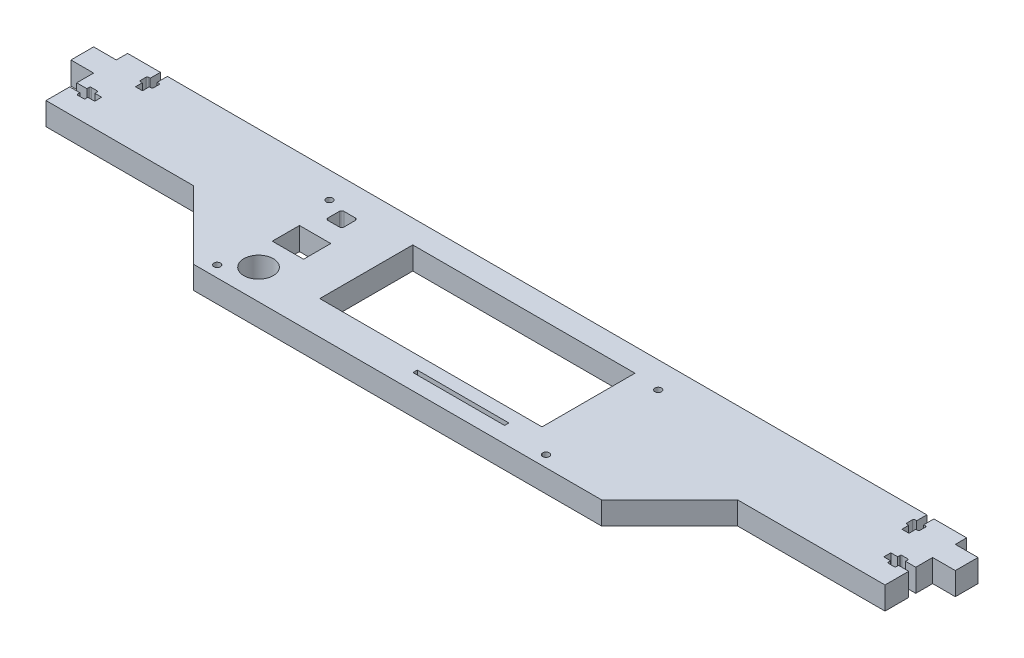
SolidWorks part; units mm, degrees
ref_plane "Front Plane" through (0, 0, 0) normal (0, 0, 1) x (1, 0, 0)
ref_plane "Top Plane" through (0, 0, 0) normal (0, 1, 0) x (1, 0, 0)
ref_plane "Right Plane" through (0, 0, 0) normal (1, 0, 0) x (0, 0, -1)
sketch "Sketch1" plane through (0, 0, 0) normal (0, 1, 0) x (1, 0, 0)
  line L0 (0, 18) -> (0, -18) construction
  line L1 (-185, 18) -> (0, 18)
  line L2 (-185, 18) -> (-185, 13)
  line L3 (-185, -18) -> (0, -18)
  line L4 (0, 18) -> (0, -18)
  line L5 (-185, 18) -> (0, 0) construction
  line L6 (-185, -18) -> (0, 0) construction
  line L7 (-185, 13) -> (-195, 13)
  line L8 (-195, 13) -> (-195, 3)
  line L9 (-195, 3) -> (-185, 3)
  line L10 (-185, 3) -> (-185, -18)
  point P0 (0, 0)
  dimension "D6" = 10
  dimension "D7" = 10
  dimension "D1" = 185
  dimension "D2" = 36
  dimension "D4" = 5
  dimension "D9" = 18
extrude "MainShape" add sketch "Sketch1" along normal blind 10 contours L2 L7 L8 L9 region at (-93.9423, 0, -0.1183)
sketch "Sketch2" plane through (0, 10, 0) normal (0, 1, 0) x (1, 0, 0)
  line L0 (-169, 18) -> (-169, 7) construction
  line L1 (-185, 18) -> (0, 18) construction
  line L2 (-170.55, 18) -> (-170.55, 13.5)
  line L3 (-170.55, 13.5) -> (-171.35, 13.5)
  line L4 (-171.85, 13) -> (-171.85, 10.5)
  line L5 (-171.35, 10) -> (-170.55, 10)
  line L6 (-170.55, 10) -> (-170.55, 7)
  line L7 (-170.55, 7) -> (-167.45, 7)
  line L8 (-185, 18) -> (-185, 13) construction
  line L9 (-170.55, 18) -> (-167.45, 18)
  line L10 (-167.45, 10) -> (-167.45, 7)
  line L11 (-166.65, 10) -> (-167.45, 10)
  line L12 (-166.15, 13) -> (-166.15, 10.5)
  line L13 (-167.45, 13.5) -> (-166.65, 13.5)
  line L14 (-167.45, 18) -> (-167.45, 13.5)
  line L16 (-185, -6) -> (-174, -6) construction
  line L50 (-185, 3) -> (-185, -18) construction
  line L51 (-174, -7.55) -> (-174, -4.45)
  line L52 (-174, -4.45) -> (-177, -4.45)
  line L53 (-177, -4.45) -> (-177, -3.5)
  line L54 (-177.5, -3) -> (-180, -3)
  line L55 (-180.5, -3.5) -> (-180.5, -4.45)
  line L56 (-180.5, -4.45) -> (-185, -4.45)
  line L57 (-185, -4.45) -> (-185, -7.55)
  line L58 (-195, 13) -> (-195, 3) construction
  line L59 (-180.5, -7.55) -> (-185, -7.55)
  line L60 (-180.5, -8.5) -> (-180.5, -7.55)
  line L61 (-177.5, -9) -> (-180, -9)
  line L62 (-177, -7.55) -> (-177, -8.5)
  line L63 (-174, -7.55) -> (-177, -7.55)
  arc A0 (-171.85, 10.5) -> (-171.35, 10) centre (-171.35, 10.5) ccw
  arc A1 (-171.35, 13.5) -> (-171.85, 13) centre (-171.35, 13) ccw
  arc A2 (-166.65, 13.5) -> (-166.15, 13) centre (-166.65, 13) cw
  arc A3 (-166.15, 10.5) -> (-166.65, 10) centre (-166.65, 10.5) cw
  arc A16 (-177, -3.5) -> (-177.5, -3) centre (-177.5, -3.5) ccw
  arc A17 (-180, -3) -> (-180.5, -3.5) centre (-180, -3.5) ccw
  arc A18 (-180, -9) -> (-180.5, -8.5) centre (-180, -8.5) cw
  arc A19 (-177, -8.5) -> (-177.5, -9) centre (-177.5, -8.5) cw
  point P14 (-171.85, 10)
  point P17 (-171.85, 13.5)
  point P28 (-166.15, 13.5)
  point P29 (-166.15, 10)
  point P34 (-195, 8)
  point P45 (-177, -3)
  point P48 (-180.5, -3)
  dimension "D8" = 0.5
  dimension "D16" = 0.5
  dimension "D1" = 11
  dimension "D2" = 1.55
  dimension "D3" = 1.55
  dimension "D4" = 8
  dimension "D5" = 2.85
  dimension "D6" = 3.5
  dimension "D7" = 16
  dimension "D9" = 11
  dimension "D10" = 8
  dimension "D11" = 3.5
  dimension "D12" = 3
  dimension "D13" = 1.55
  dimension "D14" = 1.55
  dimension "D15" = 14
extrude "ScrewSlots" cut sketch "Sketch2" against normal through all
mirror "Mirror1" about plane through (0, 0, 0) normal (1, 0, 0) of "ScrewSlots", "MainShape"
sketch "Sketch6" plane through (0, 10, 0) normal (0, 1, 0) x (1, 0, 0)
  line L0 (0, -18) -> (0, -48) construction
  line L2 (-185, -18) -> (185, -18) construction
  line L3 (90, -48) -> (-90, -48)
  line L4 (-90, -48) -> (-120, -18)
  line L5 (90, -48) -> (120, -18)
  line L6 (-120, -18) -> (120, -18)
  dimension "D1" = 135
  dimension "D2" = 30
  dimension "D3" = 90
extrude "Boss-Extrude1" add sketch "Sketch6" against normal through all
sketch "Sketch8" plane through (0, 10, 0) normal (0, 1, 0) x (1, 0, 0)
  line L0 (-71.5, 4.8833) -> (-77.5, 4.8833) construction
  line L1 (-77, -1.6167) -> (-72, -1.6167)
  line L2 (-78, -0.6167) -> (-78, 4.3833)
  line L3 (-77, 5.3833) -> (-72, 5.3833)
  line L4 (-71, -0.6167) -> (-71, 4.3833)
  line L5 (-78, -1.6167) -> (-71, 5.3833) construction
  line L6 (-78, 5.3833) -> (-71, -1.6167) construction
  line L7 (-71.5, -1.1167) -> (-71.5, 4.8833) construction
  circle A0 centre (-74.5, -34.7667) radius 6.5
  circle A1 centre (-74.5, -15.8167) radius 5.5
  arc A2 (-77, -1.6167) -> (-78, -0.6167) centre (-77, -0.6167) cw
  circle A3 centre (-74.5, -34.7667) radius 6 construction
  circle A4 centre (-74.5, -15.8167) radius 3.5 construction
  arc A5 (-72, -1.6167) -> (-71, -0.6167) centre (-72, -0.6167) ccw
  arc A6 (-72, 5.3833) -> (-71, 4.3833) centre (-72, 4.3833) cw
  arc A7 (-78, 4.3833) -> (-77, 5.3833) centre (-77, 4.3833) cw
  point P6 (-74.5, 1.8833)
  dimension "D1" = 0.5
  dimension "D2" = 2
  dimension "D3" = 0.5
  dimension "D5" = 1
  dimension "D4" = 0.5
extrude "Cut-Extrude2" cut sketch "Sketch8" against normal through all
sketch "Sketch7" plane through (0, 10, 0) normal (0, 1, 0) x (1, 0, 0)
  circle A0 centre (60.5, -43.0167) radius 1.45
  circle A1 centre (-84.5, -43.0167) radius 1.45
  circle A2 centre (-84.5, 6.4833) radius 1.45
  circle A3 centre (60.5, 6.4833) radius 1.45
  dimension "D1" = 2.9
  dimension "D2" = 2.9
  dimension "D3" = 2.9
  dimension "D4" = 2.9
extrude "Cut-Extrude1" cut sketch "Sketch7" against normal through all
sketch "Sketch9" plane through (0, 10, 0) normal (0, 1, 0) x (1, 0, 0)
  line L0 (0, 7.2333) -> (0, -32.7667) construction
  line L1 (48.5, 7.2333) -> (-48.5, 7.2333) construction
  line L2 (-48.5, -32.7667) -> (48.5, -32.7667) construction
  line L3 (-48.5, -12.7667) -> (48.5, -12.7667) construction
  line L4 (-48.5, 7.2333) -> (-48.5, -32.7667) construction
  line L5 (48.5, -32.7667) -> (48.5, 7.2333) construction
  line L7 (-49, -33.2667) -> (49, -33.2667)
  line L8 (-49, -33.2667) -> (-49, 7.7333)
  line L9 (-49, 7.7333) -> (49, 7.7333)
  line L10 (49, -33.2667) -> (49, 7.7333)
  line L11 (-49, -33.2667) -> (49, 7.7333) construction
  line L12 (-49, 7.7333) -> (49, -33.2667) construction
  point P12 (0, -12.7667)
  dimension "D1" = 0.5
  dimension "D2" = 0.5
extrude "Cut-Extrude3" cut sketch "Sketch9" against normal through all and the other way through all
sketch "Sketch10" plane through (0, 10, 0) normal (0, 1, 0) x (1, 0, 0)
  line L0 (20, -39.2667) -> (20, -40.7667) construction
  line L1 (40, -39.2667) -> (0, -39.2667) construction
  line L2 (0, -40.7667) -> (40, -40.7667) construction
  line L3 (0, -40.0167) -> (40, -40.0167) construction
  line L4 (0, -39.2667) -> (0, -40.7667) construction
  line L5 (40, -40.7667) -> (40, -39.2667) construction
  line L7 (-0.2, -40.9667) -> (40.2, -40.9667)
  line L8 (-0.2, -40.9667) -> (-0.2, -39.0667)
  line L9 (-0.2, -39.0667) -> (40.2, -39.0667)
  line L10 (40.2, -40.9667) -> (40.2, -39.0667)
  line L11 (-0.2, -40.9667) -> (40.2, -39.0667) construction
  line L12 (-0.2, -39.0667) -> (40.2, -40.9667) construction
  point P12 (20, -40.0167)
  dimension "D1" = 0.2
  dimension "D2" = 0.2
extrude "Cut-Extrude4" cut sketch "Sketch10" against normal through all
sketch "Sketch12" plane through (0, 0, 0) normal (0, -1, 0) x (-1, 0, 0)
  line L1 (81.4, -9.8167) -> (67.6, -9.8167)
  line L2 (81.4, -9.8167) -> (81.4, -21.8167)
  line L3 (81.4, -21.8167) -> (67.6, -21.8167)
  line L4 (67.6, -9.8167) -> (67.6, -21.8167)
  line L5 (81.4, -9.8167) -> (67.6, -21.8167) construction
  line L6 (81.4, -21.8167) -> (67.6, -9.8167) construction
  point P0 (74.5, -15.8167)
  dimension "D1" = 13.8
  dimension "D2" = 12
extrude "PotentiometerAdjustment" cut sketch "Sketch12" against normal through all
sketch "Sketch11" [suppressed] plane through (0, 0, 0) normal (0, -1, 0) x (1, 0, 0)
  line L1 (-149.5, -2.5) -> (-167.5, -2.5)
  line L2 (-147.5, -0.5) -> (-147.5, 6.5)
  line L3 (-149.5, 8.5) -> (-167.5, 8.5)
  line L4 (-169.5, -0.5) -> (-169.5, 6.5)
  line L5 (-147.5, -2.5) -> (-169.5, 8.5) construction
  line L6 (-147.5, 8.5) -> (-169.5, -2.5) construction
  line L7 (170.75, -7.5) -> (167.25, -7.5) construction
  line L8 (-174.5, 7.75) -> (-174.5, 4.25) construction
  arc A0 (-147.5, 6.5) -> (-149.5, 8.5) centre (-149.5, 6.5) ccw
  arc A1 (-167.5, 8.5) -> (-169.5, 6.5) centre (-167.5, 6.5) ccw
  arc A2 (-167.5, -2.5) -> (-169.5, -0.5) centre (-167.5, -0.5) cw
  arc A3 (-149.5, -2.5) -> (-147.5, -0.5) centre (-149.5, -0.5) ccw
  point P0 (-158.5, 3)
  dimension "D3" = 2
  dimension "D1" = 22
  dimension "D2" = 11
  dimension "D4" = 5
  dimension "D5" = 5
extrude "LCDCableCutout" [suppressed] cut sketch "Sketch11" against normal through all
equation "\"Y-ROD-SPACING\"=75"
equation "\"Y-BED-OFFSET\"=2"
equation "\"Y-BED-ROD-INSET\"=3.5"
equation "\"T-SLOT-NUT-FILLET-RADIUS\"=0.5"
equation "\"T-SLOT-SCREW-SHAFT-RADIUS\"=1.55"
equation "\"T-SLOT-SCREW-SHAFT-CUTOUT-LENGTH\"=11.0"
equation "\"T-SLOT-NUT-DEPTH\"=3.5"
equation "\"T-SLOT-NUT-WIDTH\"=2.85"
equation "\"T-SLOT-NUT-END-DISTANCE\"=8"
equation "\"ACRYLIC-TAB-CUTOUT-SIZE\"=\"ACRYLIC-THICKNESS\"+\"ACRYLIC-TAB-TOLERANCE\"*2"
equation "\"ACRYLIC-M3-HOLE\"=2.9"
equation "\"SMOOTHROD-CAP-SCREW-DISTANCE\"=20"
equation "\"D2@Sketch2\"=\"T-SLOT-SCREW-SHAFT-RADIUS\""
equation "\"D1@Sketch2\"=\"T-SLOT-SCREW-SHAFT-CUTOUT-LENGTH\""
equation "\"D6@Sketch2\"=\"T-SLOT-NUT-DEPTH\""
equation "\"D5@Sketch2\"=\"T-SLOT-NUT-WIDTH\""
equation "\"D3@Sketch2\"=\"T-SLOT-SCREW-SHAFT-RADIUS\""
equation "\"D8@Sketch2\"=\"T-SLOT-NUT-FILLET-RADIUS\""
equation "\"D4@Sketch2\"=\"T-SLOT-NUT-END-DISTANCE\""
equation "\"D11@Sketch2\"=\"T-SLOT-NUT-DEPTH\""
equation "\"D10@Sketch2\"=\"T-SLOT-NUT-END-DISTANCE\""
equation "\"D13@Sketch2\"=\"T-SLOT-SCREW-SHAFT-RADIUS\""
equation "\"D14@Sketch2\"=\"T-SLOT-SCREW-SHAFT-RADIUS\""
equation "\"D16@Sketch2\"=\"T-SLOT-NUT-FILLET-RADIUS\""
equation "\"D9@Sketch2\"=\"T-SLOT-SCREW-SHAFT-CUTOUT-LENGTH\""
equation "\"ACRYLIC-TAB-WIDTH\"=\"ACRYLIC-THICKNESS\""
equation "\"D6@Sketch1\"=\"ACRYLIC-TAB-WIDTH\""
equation "\"D7@Sketch1\"=\"ACRYLIC-TAB-WIDTH\""
equation "\"FRAME-WIDTH-INNER\"=370"
equation "\"D1@Sketch1\"=\"FRAME-WIDTH-INNER\"/2"
equation "\"X-ROD-SPACING\"=45"
equation "\"Z-ROD-SPACING\"=17.5"
equation "\"ACRYLIC-THICKNESS\"=10"
equation "\"ACRYLIC-THICKNESS2\"=4.5"
equation "\"NEMA17-HOLE-SPACING\"=31"
equation "\"NEMA17-CENTRAL-CUTOUT\"=22.5"
equation "\"Z-BRACKET-REACH\"=55"
equation "\"TOP-BRACKET-SPACING\"=40"
equation "\"SMOOTHROD-X-LENGTH\"=350"
equation "\"SMOOTHROD-Y-LENGTH\"=350"
equation "\"SMOOTHROD-Z-LENGTH\"=350"
equation "\"SMOOTHROD-TIGHTENING-HEADROOM\"=.25"
equation "\"LEADSCREW-Z-LENGTH\"=300"
equation "\"SCREW-LENGTH-FRAME\"=\"ACRYLIC-THICKNESS\" + 10"
equation "\"SCREW-HEAD-RADIUS\"=6"
equation "\"PRINTED-X-SMOOTHROD-DIAMETER\"=9.0"
equation "\"PRINTED-X-SMOOTHROD-CUTOUT\"=10"
equation "\"PRINTED-X-BASE-HEIGHT\"=10"
equation "\"PRINTED-LM8UU-CUTOUT-SIZE\"=15.5"
equation "\"PRINTED-LM8UU-CUTOUT-LENGTH\"=24.5"
equation "\"PRINTED-X-IDLER-HEIGHT\"=16"
equation "\"PSU-MOUNTING-WIDTH\"=95"
equation "\"PSU-MOUNTING-HEIGHT\"=177"
equation "\"D1@MainShape\"=\"ACRYLIC-THICKNESS\""
equation "\"Y-BELT-TO-ROD-DISTANCE\"=20"
equation "\"SPOOL-HOLDER-ROD-SPACING\"=150"
equation "\"Z-ROD-INSET\"=16"
equation "\"D7@Sketch2\"=\"Z-ROD-INSET\""
equation "\"D1@Sketch7\"=\"ACRYLIC-M3-HOLE\""
equation "\"D2@Sketch7\"=\"ACRYLIC-M3-HOLE\""
equation "\"D3@Sketch7\"=\"ACRYLIC-M3-HOLE\""
equation "\"D4@Sketch7\"=\"ACRYLIC-M3-HOLE\""
equation "\"Y-BED-SCREW-SPACING\"=209"
equation "\"Y-BED-SCREW-CUTOUT-SLOT-HEIGHT\"=2"
equation "\"ACRYLIC-TAB-TOLERANCE\"=-.05"
equation "\"SCREW-LENGTH-MOTOR\"=\"ACRYLIC-THICKNESS\" + 5"
equation "\"SCREW-LENGTH-EXTRUDER\"=28"
equation "\"PRINTED-M3-HOLE\"=3.5"
equation "\"PRINTED-M3-NUT-AF\"=6.25"
equation "\"ACRYLIC-X-CARRIAGE-WIDTH\"=55"
equation "\"ACRYLIC-X-CARRIAGE-HEIGHT\"=75"
equation "\"ACRYLIC-X-CARRIAGE-LM8UU-CUTOUT-WIDTH\"=24.25"
equation "\"ACRYLIC-X-CARRIAGE-LM8UU-CUTOUT-HEIGHT\"=11.0"
equation "\"ACRYLIC-X-CARRIAGE-SCREW-SPACING-X\"=15"
equation "\"ACRYLIC-X-CARRIAGE-SCREW-SPACING-Y\"=33"
equation "\"ACRYLIC-X-CARRIAGE-CENTER-TAB-SPACING\"=14"
equation "\"ACRYLIC-X-CARRIAGE-EXTRUDER-OFFSET\"=26"
equation "\"ACRYLIC-X-CARRIAGE-EXTRUDER-ANGLE\"=90"
equation "\"ACRYLIC-X-CARRIAGE-EXTRUDER-SHELF-DEPTH\"=\"ACRYLIC-X-CARRIAGE-EXTRUDER-OFFSET\" + 28"
equation "\"ACRYLIC-X-CARRIAGE-EXTRUDER-BRACE-SPACING\"=23"
equation "\"ACRYLIC-X-CARRIAGE-EXTRUDER-BRACE-TAB-OFFSET\"=20"
equation "\"ACRYLIC-X-CARRIAGE-EXTRUDER-BRACE-HEIGHT\"=35"
equation "\"ACRYLIC-X-CARRIAGE-EXTRUDER-BRACE-SCREW-SPACING\"=22"
equation "\"ACRYLIC-X-CARRIAGE-DUAL-WIDTH-MULTIPLIER\"=1.65"
equation "\"ACRYLIC-X-CARRIAGE-DUAL-HOTEND-SPACING\"=42"
equation "\"ACRYLIC-X-CARRIAGE-DUAL-WIDTH\"=75"
equation "\"ACRYLIC-X-CARRIAGE-DUAL-HOTEND-SEPARATION\"=36"
equation "\"ACRYLIC-X-CARRIAGE-DUAL-MOUNT-PLATE-DEPTH\"=75"
equation "\"ACRYLIC-X-CARRIAGE-DUAL-MOUNT-BRACE-WIDTH\"=33"
equation "\"ACRYLIC-X-CARRIAGE-DUAL-MOUNT-SCREW-WIDTH\"=40"
equation "\"BLOWER-FAN-WIDTH\"=15"
